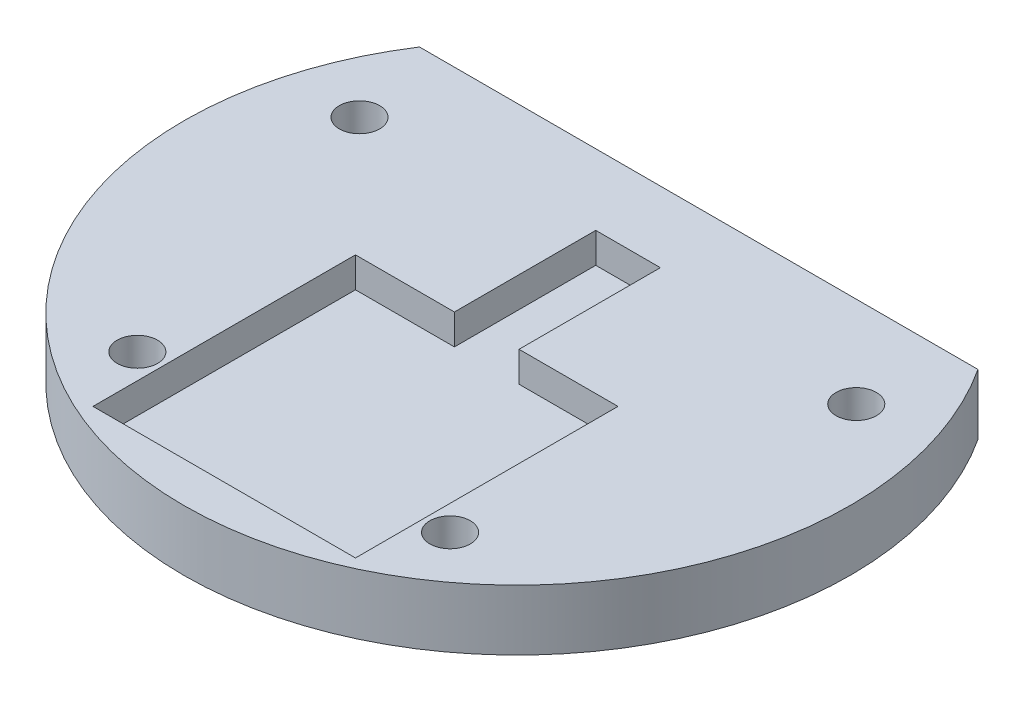
SolidWorks part; units mm, degrees
ref_plane "前视基准面" through (0, 0, 0) normal (0, 0, 1) x (1, 0, 0)
ref_plane "上视基准面" through (0, 0, 0) normal (0, 1, 0) x (1, 0, 0)
ref_plane "右视基准面" through (0, 0, 0) normal (1, 0, 0) x (0, 0, -1)
other "Configuration Table"
sketch "草图1" plane through (0, 0, 0) normal (0, 1, 0) x (1, 0, 0)
  circle A0 centre (0, 0) radius 16.5
  dimension "D1" = 33
extrude "凸台-拉伸1" add sketch "草图1" along normal blind 3
sketch "草图2" plane through (0, 3, 0) normal (0, 1, 0) x (1, 0, 0)
  line L1 (6.5, -14.5) -> (-6.5, -14.5)
  line L2 (6.5, -14.5) -> (6.5, -1.5)
  line L3 (6.5, -1.5) -> (-6.5, -1.5)
  line L4 (-6.5, -14.5) -> (-6.5, -1.5)
  line L5 (-6.5, -1.5) -> (6.5, -14.5) construction
  line L6 (0, -8) -> (0, 0)
  dimension "D1" = 13
  dimension "D2" = 8
extrude "切除-拉伸1" cut sketch "草图2" against normal blind 1.5 contours L3 L4 L1 L2
sketch "草图3" plane through (0, 3, 0) normal (0, 1, 0) x (1, 0, 0)
  line L0 (6.5, -1.5) -> (-6.5, -1.5) construction
  line L1 (1.6, -1.5) -> (-1.6, -1.5)
  line L2 (1.6, -1.5) -> (1.6, 5.5)
  line L3 (1.6, 5.5) -> (-1.6, 5.5)
  line L4 (-1.6, -1.5) -> (-1.6, 5.5)
  line L9 (0, 0) -> (0, 5.5) construction
  dimension "D1" = 3.2
  dimension "D2" = 7
extrude "切除-拉伸2" cut sketch "草图3" against normal up to surface (1.5 mm away) up to face at (0, 1.5, 8)
sketch "草图4" plane through (0, 0, 0) normal (0, -1, 0) x (1, 0, 0)
  circle A0 centre (-7.7433, 11.0586) radius 1
  circle A1 centre (7.7433, 11.0586) radius 1
  circle A2 centre (7.7433, 11.0586) radius 1.5
  circle A3 centre (-7.7433, 11.0586) radius 1.5
  circle A4 centre (-12.3, -4.5) radius 1.5
  circle A5 centre (-12.3, -4.5) radius 1
  circle A6 centre (12.3, -4.5) radius 1.5
  circle A7 centre (12.3, -4.5) radius 1
  dimension "D1" = 2
  dimension "D2" = 3
extrude "切除-拉伸3" cut sketch "草图4" against normal blind 1
extrude "切除-拉伸4" cut sketch "草图4<2>" against normal through all contours A1 | A0 | A5 | A7 region at (7.7433, 0, 11.0586)
sketch "草图4<2>" plane through (0, 0, 0) normal (0, -1, 0) x (1, 0, 0) same geometry as "草图4"
sketch "草图5" plane through (0, 3, 0) normal (0, 1, 0) x (1, 0, 0)
  line L1 (13.8293, 9) -> (-13.8293, 9)
  line L2 (13.8293, 9) -> (13.8293, 18.0518)
  line L3 (13.8293, 18.0518) -> (-13.8293, 18.0518)
  line L4 (-13.8293, 9) -> (-13.8293, 18.0518)
  circle A0 centre (0, 0) radius 16.5 construction
  dimension "D1" = 9
extrude "切除-拉伸5" cut sketch "草图5" against normal through all
